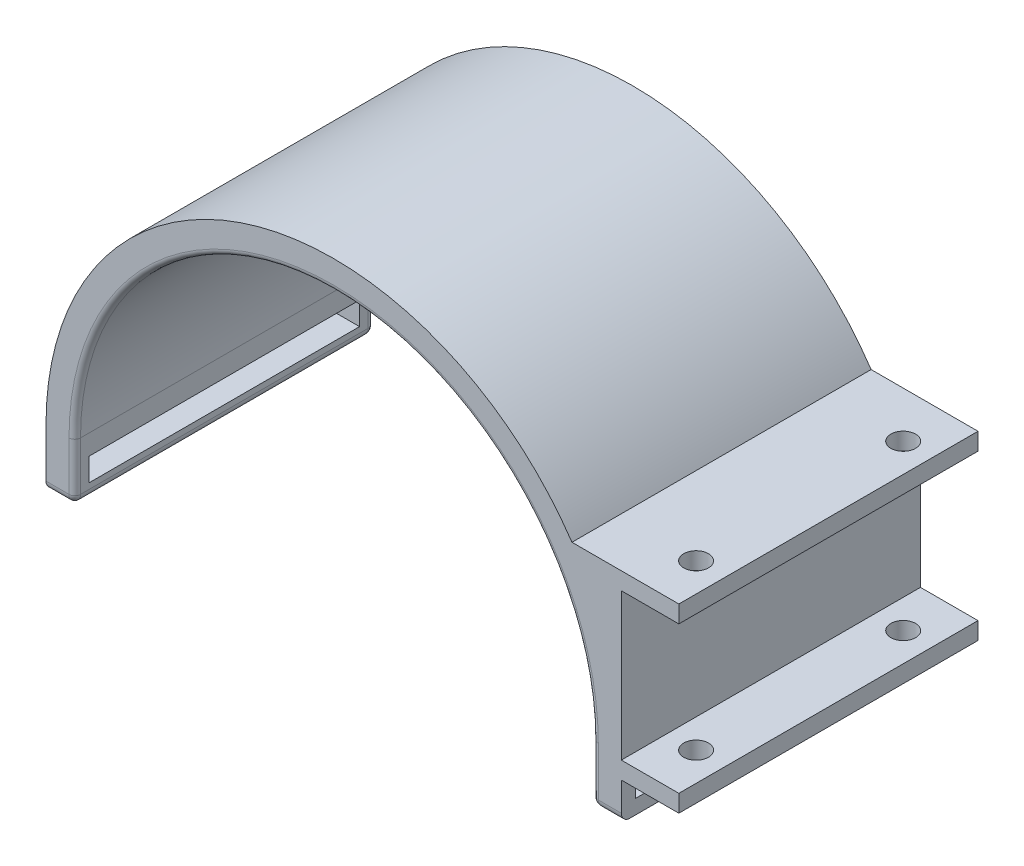
SolidWorks part; units mm, degrees
ref_plane "Front Plane" through (0, 0, 0) normal (0, 0, 1) x (1, 0, 0)
ref_plane "Top Plane" through (0, 0, 0) normal (0, 1, 0) x (1, 0, 0)
ref_plane "Right Plane" through (0, 0, 0) normal (1, 0, 0) x (0, 0, -1)
sketch "Sketch1" plane through (0, 0, 0) normal (0, 0, 1) x (1, 0, 0)
  line L0 (0, 0) -> (90, 0) construction
  line L1 (45, 45) -> (45, 0) construction
  line L2 (0, 0) -> (-5, 0)
  line L3 (90, 0) -> (95, 0)
  line L4 (45, 50) -> (45, 45) construction
  line L5 (95, -10) -> (90, -10)
  line L6 (-5, 0) -> (0, 0)
  line L7 (-5, 0) -> (-5, -10)
  line L8 (-5, -10) -> (0, -10)
  line L9 (0, 0) -> (0, -10)
  line L10 (90, 0) -> (90, -10)
  line L11 (95, 0) -> (90, 0)
  line L12 (95, 0) -> (95, -10)
  arc A0 (0, 0) -> (90, 0) centre (45, 0) cw
  arc A1 (-5, 0) -> (95, 0) centre (45, 0) cw
  dimension "D1" = 90
  dimension "D2" = 45
  dimension "D3" = 5
  dimension "D4" = 5
  dimension "D5" = 10
extrude "Boss-Extrude1" add sketch "Sketch1" along normal blind 52 contours A1 L2 A0 L3 | L12 L3 L10 L5 | L9 L2 L7 L8 region at (-2.5, -5, 0) region at (-2.5, 1.118, 0) region at (92.5, -5, 0)
sketch "Sketch3" plane through (95, 0, 0) normal (1, 0, 0) x (0, 0, -1)
  line L0 (0, 0) -> (0, -10) construction
  line L1 (-49.5, -3.5) -> (-2.5, -3.5)
  line L2 (-49.5, -3.5) -> (-49.5, -7.5)
  line L3 (-49.5, -7.5) -> (-2.5, -7.5)
  line L4 (-2.5, -3.5) -> (-2.5, -7.5)
  line L5 (-52, 0) -> (-52, -10) construction
  line L6 (-52, -10) -> (0, -10) construction
  dimension "D1" = 2.5
  dimension "D2" = 2.5
  dimension "D3" = 2.5
  dimension "D4" = 4
extrude "Cut-Extrude1" cut sketch "Sketch3" against normal through all
sketch "Sketch4" plane through (95, 0, 0) normal (1, 0, 0) x (0, 0, -1)
  line L0 (-2.5, -3.5) -> (0, -3.5) construction
  line L1 (0, 0) -> (0, -10) construction
  line L2 (-52, 50) -> (-52, 0) construction
  line L3 (0, -3.5) -> (-52, -3.5)
  line L4 (0, -3.5) -> (0, 28)
  line L5 (0, 28) -> (-52, 28)
  line L6 (-52, -3.5) -> (-52, 28)
  dimension "D1" = 31.5
extrude "Boss-Extrude3" add sketch "Sketch4" against normal up to next
sketch "Sketch5" plane through (95, 0, 0) normal (1, 0, 0) x (0, 0, -1)
  line L0 (-2.5, -3.5) -> (0, -3.5) construction
  line L1 (0, 28) -> (0, -10) construction
  line L2 (-52, 28) -> (-52, -10) construction
  line L3 (0, -3.5) -> (-52, -3.5)
  line L4 (0, -3.5) -> (0, -0.5)
  line L5 (0, -0.5) -> (-52, -0.5)
  line L6 (-52, -3.5) -> (-52, -0.5)
  line L8 (0, 28) -> (-52, 28)
  line L9 (0, 28) -> (0, 25)
  line L10 (0, 25) -> (-52, 25)
  line L11 (-52, 28) -> (-52, 25)
  dimension "D1" = 3
  dimension "D2" = 3
extrude "Boss-Extrude4" add sketch "Sketch5" along normal blind 10
sketch "Sketch7" plane through (0, 28, 0) normal (0, 1, 0) x (1, 0, 0)
  line L0 (100, 0) -> (100, -52) construction
  line L3 (86.4246, 0) -> (105, 0) construction
  line L4 (86.4246, -52) -> (105, -52) construction
  line L5 (105, 0) -> (105, -52) construction
  line L6 (105, -26) -> (86.4246, -26) construction
  line L7 (86.4246, -52) -> (86.4246, 0) construction
  circle A0 centre (100, -44) radius 2.15
  circle A1 centre (100, -8) radius 2.15
  dimension "D2" = 4.3
  dimension "D3" = 8
  dimension "D1" = 5
extrude "Cut-Extrude3" cut sketch "Sketch7" against normal through all
fillet "Fillet1" radius 1 6 edges at (0, -5, 52) (90, -5, 52) (0, -5, 0) (90, -5, 0) (45, 45, 52) (45, 45, 0)
fillet "Fillet2" radius 1.5 10 edges at (93, -10, 52) (90.2929, -10, 51.7071) (93, -10, 0) (90.2929, -10, 0.2929) (-3, -10, 52) (-0.2929, -10, 51.7071) (-3, -10, 0) (-0.2929, -10, 0.2929) (90, -10, 26) (0, -10, 26)
